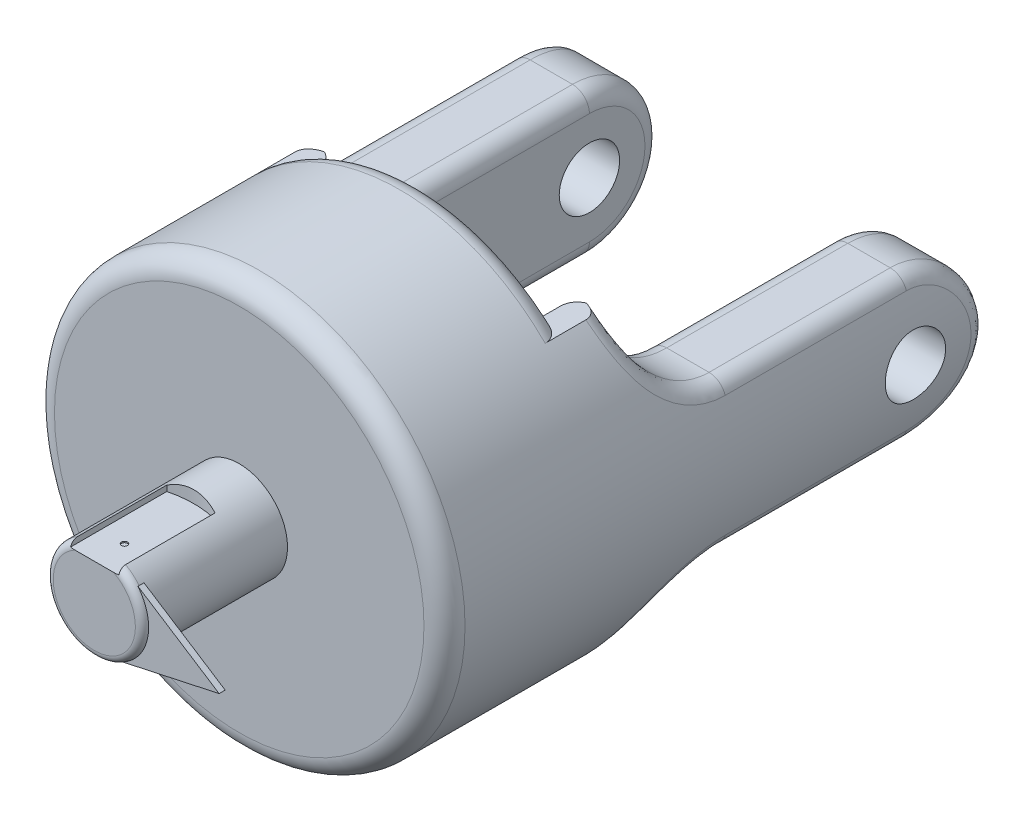
SolidWorks part; units mm, degrees
material "Ductile Iron (SN)"
ref_plane "Front Plane" through (0, 0, 0) normal (0, 0, 1) x (1, 0, 0)
ref_plane "Top Plane" through (0, 0, 0) normal (0, 1, 0) x (1, 0, 0)
ref_plane "Right Plane" through (0, 0, 0) normal (1, 0, 0) x (0, 0, -1)
sketch "Sketch2" plane through (0, 0, 0) normal (0, 0, 1) x (1, 0, 0)
  circle A0 centre (0, 0) radius 17
  dimension "D1" = 34
extrude "Boss-Extrude1" add sketch "Sketch2" along normal blind 45
sketch "Sketch3" plane through (0, 0, 0) normal (0, 1, 0) x (1, 0, 0)
  line L0 (17, 0) -> (-17, 0) construction
  line L1 (-10, 0) -> (10, 0)
  line L2 (-10, 0) -> (-10, -30)
  line L3 (-10, -30) -> (10, -30)
  line L4 (10, 0) -> (10, -30)
  line L5 (-10, 0) -> (10, -30) construction
  line L6 (-10, -30) -> (10, 0) construction
  point P0 (0, -15)
  dimension "D1" = 20
  dimension "D2" = 30
  dimension "D3" = 15
extrude "Cut-Extrude1" cut sketch "Sketch3" against normal mid plane 40
sketch "Sketch4" plane through (0, 0, 0) normal (1, 0, 0) x (0, 0, -1)
  line L0 (26.7759, 0) -> (-60.0941, 0) construction
  line L1 (0, -13.7477) -> (0, 13.7477) construction
  line L20 (-6, 6) -> (-21, 6)
  line L26 (-30, 22) -> (4, 22)
  line L27 (4, 22) -> (4, -22)
  line L28 (4, 0) -> (0, 0)
  line L29 (-27, 12) -> (-30, 12)
  line L31 (-30, 12) -> (-30, 22)
  line L32 (-6, -6) -> (-21, -6)
  line L33 (-30, -22) -> (4, -22)
  line L34 (-30, -12) -> (-30, -22)
  line L35 (-27, -12) -> (-30, -12)
  arc A3 (-6, -6) -> (-6, 6) centre (-6, 0) ccw
  arc A5 (-21, 6) -> (-27, 12) centre (-21, 12) cw
  arc A6 (-21, -6) -> (-27, -12) centre (-21, -12) ccw
  dimension "D1" = 6
  dimension "D3" = 3
  dimension "D4" = 15
  dimension "D2" = 30
  dimension "D5" = 6
  dimension "D6" = 34
  dimension "D7" = 10
extrude "Cut-Extrude5" cut sketch "Sketch4" against normal mid plane 40 contours A5 L20 A3 L28 L27 L26 L31 L29 | L32 A6 L35 L34 L33 L27 L28 A3 region at (0, 13.646, 11.4966) region at (0, -13.646, 11.4966)
sketch "Sketch6" plane through (0, 0, 0) normal (1, 0, 0) x (0, 0, -1)
  circle A0 centre (-6, 0) radius 2.5
  dimension "D1" = 5
extrude "Cut-Extrude7" cut sketch "Sketch6" against normal mid plane 50
sketch "Sketch7" plane through (0, 0, 45) normal (0, 0, 1) x (1, 0, 0)
  circle A0 centre (0, 0) radius 4
  dimension "D1" = 8
extrude "Boss-Extrude2" add sketch "Sketch7" along normal blind 12
ref_plane "Plane1" through (0, 4, 0) normal (0, 1, 0) x (1, 0, 0)
sketch "Sketch9" plane through (0, 4, 0) normal (0, 1, 0) x (1, 0, 0)
  line L0 (0, -57) -> (0, -45) construction
  line L1 (-4, -57) -> (4, -57) construction
  line L2 (-17, -45) -> (17, -45) construction
  line L3 (-2, -57) -> (2, -57)
  line L4 (2, -57) -> (2, -49)
  line L5 (-2, -49) -> (-2, -57)
  arc A2 (-2, -49) -> (2, -49) centre (0, -56.746) cw
  dimension "D3" = 8
  dimension "D1" = 2
  dimension "D2" = 2
  dimension "D4" = 8
extrude "Cut-Extrude10" cut sketch "Sketch9" against normal blind 1
sketch "Sketch10" plane through (0, 3, 0) normal (0, 1, 0) x (1, 0, 0)
  line L0 (-2, -57) -> (2, -57) construction
  line L1 (-2, -57) -> (-2, -49) construction
  circle A0 centre (0, -54.5) radius 0.25
  dimension "D1" = 0.5
  dimension "D2" = 2.5
  dimension "D3" = 2
extrude "Cut-Extrude11" cut sketch "Sketch10" against normal blind 0.1
fillet "Fillet2" radius 1.7 3 edges at (17, 0, 45) (0, -17, 30) (0, 17, 30)
fillet "Fillet3" radius 1.4 20 edges at (14.9515, 8.0902, 25.5512) (14.9515, -8.0902, 25.5512) (15.906, -6, 13.5) (16.992, -0.5203, 0.0226) (10, -7.7574, 25.2426) (10, -6, 13.5) (10, 0, 0) (10, 7.7574, 25.2426) (-15.4292, -7.1373, 24.5148) (-15.906, -6, 13.5) (-17, 0, 0) (-15.4292, 7.1373, 24.5148) (-10, 7.7574, 25.2426) (-10, -7.7574, 25.2426) (-10, -6, 13.5) (-10, 0, 0) (15.906, 6, 13.5) (10, 6, 13.5) (-15.906, 6, 13.5) (-10, 6, 13.5)
fillet "Fillet7" radius 0.6 1 edges at (0, -4, 57)
sketch "Sketch11" plane through (0, 0, 0) normal (0, 0, 1) x (1, 0, 0)
  line L0 (3.114, 2.5106) -> (9.8382, -1.8237)
  line L1 (9.8382, -1.8237) -> (1.8382, -3.5526)
  circle A0 centre (0, 0) radius 4 construction
  arc A1 (1.8382, -3.5526) -> (3.114, 2.5106) centre (0, 0) ccw
  dimension "D1" = 45
  dimension "D2" = 8
  dimension "D3" = 8
extrude "Boss-Extrude3" add sketch "Sketch11" along normal blind 0.5 from offset 56
